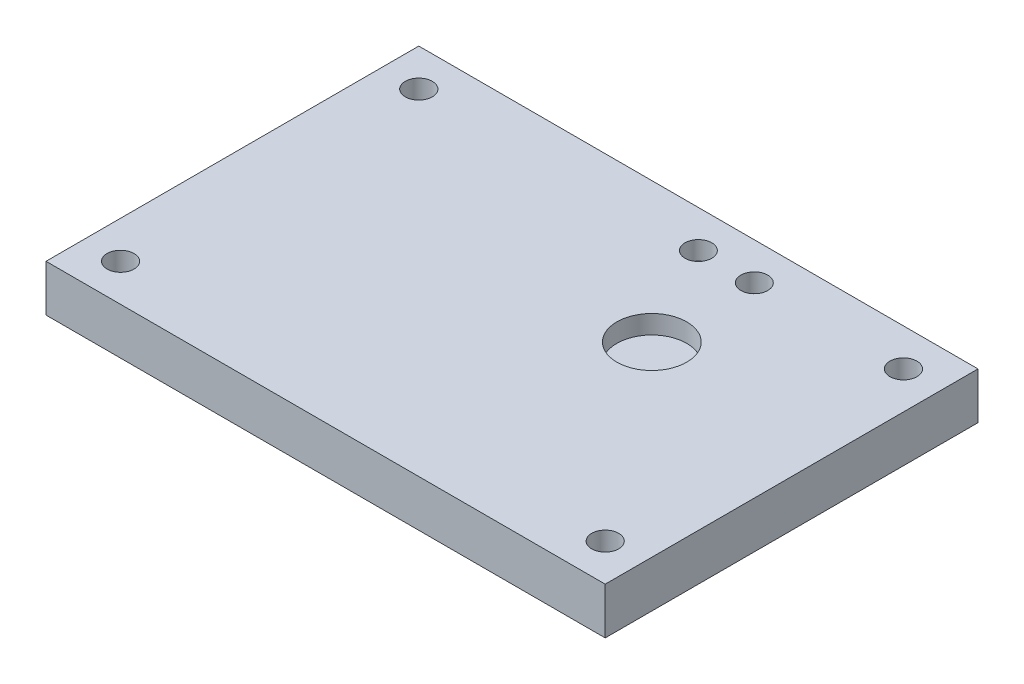
SolidWorks part; units mm, degrees
ref_plane "Front Plane" through (0, 0, 0) normal (0, 0, 1) x (1, 0, 0)
ref_plane "Top Plane" through (0, 0, 0) normal (0, 1, 0) x (1, 0, 0)
ref_plane "Right Plane" through (0, 0, 0) normal (1, 0, 0) x (0, 0, -1)
sketch "Sketch1" plane through (0, 0, 0) normal (0, 1, 0) x (1, 0, 0)
  line L1 (-38.1, 25.4) -> (38.1, 25.4)
  line L2 (-38.1, 25.4) -> (-38.1, -25.4)
  line L3 (-38.1, -25.4) -> (38.1, -25.4)
  line L4 (38.1, 25.4) -> (38.1, -25.4)
  line L5 (-38.1, 25.4) -> (38.1, -25.4) construction
  line L6 (-38.1, -25.4) -> (38.1, 25.4) construction
  point P0 (0, 0)
  dimension "D1" = 50.8
  dimension "D2" = 76.2
extrude "Boss-Extrude1" add sketch "Sketch1" along normal blind 6.35
sketch "Sketch2" plane through (0, 6.35, 0) normal (0, 1, 0) x (1, 0, 0)
  line L0 (-38.1, 25.4) -> (-38.1, -25.4) construction
  line L1 (38.1, 25.4) -> (-38.1, 25.4) construction
  line L2 (-38.1, -25.4) -> (38.1, -25.4) construction
  line L3 (38.1, -25.4) -> (38.1, 25.4) construction
  circle A0 centre (-33.02, 20.32) radius 1.8415
  circle A1 centre (-33.02, -20.32) radius 1.8415
  circle A2 centre (33.02, -20.32) radius 1.8415
  circle A3 centre (33.02, 20.32) radius 1.8415
  dimension "D3" = 3.683
  dimension "D1" = 5.08
  dimension "D2" = 5.08
  dimension "D4" = 5.08
  dimension "D5" = 5.08
extrude "Cut-Extrude1" cut sketch "Sketch2" against normal through all from offset 0
sketch "Sketch3" plane through (0, 6.35, 0) normal (0, 1, 0) x (1, 0, 0)
  line L0 (38.1, 25.4) -> (-38.1, 25.4) construction
  line L1 (38.1, -25.4) -> (38.1, 25.4) construction
  circle A0 centre (12.7, 6.35) radius 4.7625
  circle A1 centre (5.08, 20.32) radius 1.8288
  circle A2 centre (12.7, 20.32) radius 1.8288
  dimension "D4" = 9.525
  dimension "D7" = 3.6576
  dimension "D1" = 5.08
  dimension "D2" = 19.05
  dimension "D3" = 25.4
  dimension "D5" = 7.62
  dimension "D6" = 33.02
extrude "Cut-Extrude2" cut sketch "Sketch3" against normal blind 2.54 contours A0 | A1 | A2 region at (12.7, 6.35, -6.35)
